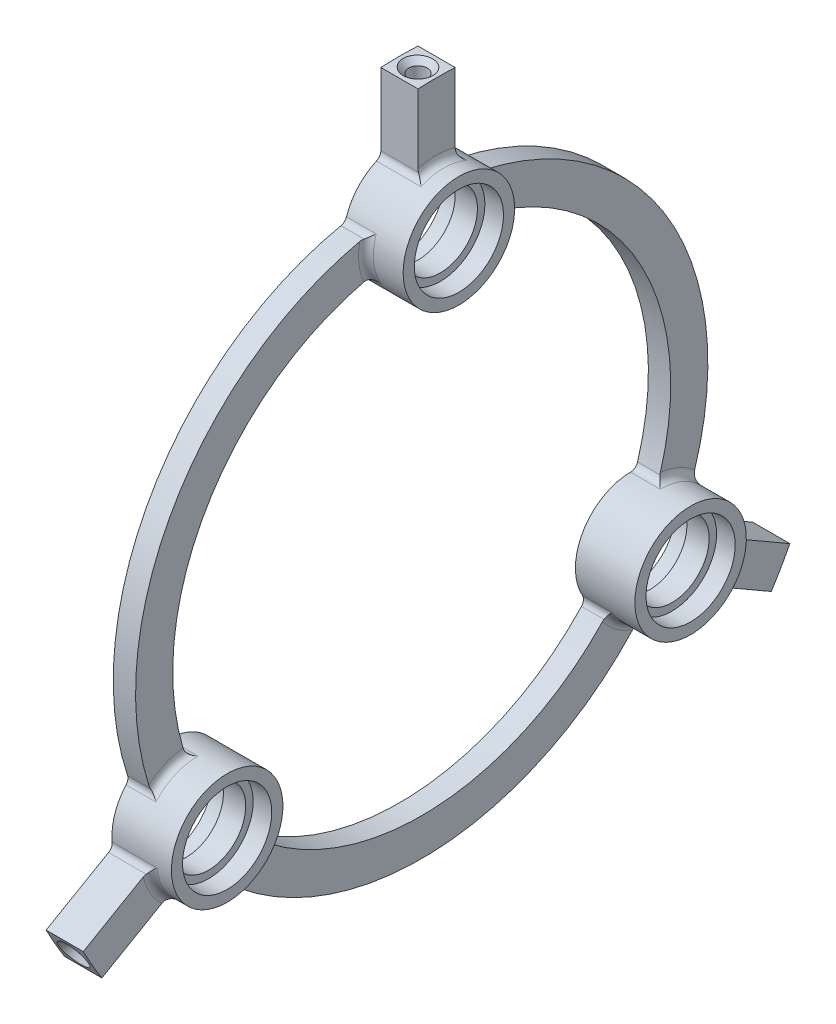
SolidWorks part; units mm, degrees
ref_plane "Спереди" through (0, 0, 0) normal (0, 0, 1) x (1, 0, 0)
ref_plane "Сверху" through (0, 0, 0) normal (0, 1, 0) x (1, 0, 0)
ref_plane "Справа" through (0, 0, 0) normal (1, 0, 0) x (0, 0, -1)
sketch "Эскиз3" plane through (0, 0, 0) normal (1, 0, 0) x (0, 0, -1)
  circle A0 centre (0, 0) radius 36 construction
  dimension "D1" = 72
sketch "Эскиз1" plane through (0, 0, 0) normal (1, 0, 0) x (0, 0, -1)
  line L0 (38.5, 0) -> (33.5, 0) construction
  circle A3 centre (0, 0) radius 38.5
  circle A4 centre (0, 0) radius 33.5
  circle A5 centre (0, 0) radius 36 construction
  point P9 (36, 0)
  dimension "D1" = 5
extrude "Бобышка-Вытянуть1" add sketch "Эскиз1" along normal blind 3
sketch "Эскиз2" plane through (0, 0, 0) normal (-1, 0, 0) x (0, 0, 1)
  circle A0 centre (0, 36) radius 7.5
  circle A1 centre (0, 0) radius 36 construction
  dimension "D1" = 15
extrude "Бобышка-Вытянуть2" add sketch "Эскиз2" against normal blind 8
sketch "Эскиз4" plane through (0, 0, 0) normal (-1, 0, 0) x (0, 0, 1)
  circle A0 centre (0, 36) radius 5
  dimension "D1" = 10
extrude "Вырез-Вытянуть1" cut sketch "Эскиз4" against normal through all
sketch "Эскиз5" plane through (0, 0, 0) normal (-1, 0, 0) x (0, 0, 1)
  circle A0 centre (0, 36) radius 6
  dimension "D1" = 12
extrude "Вырез-Вытянуть2" cut sketch "Эскиз5" against normal blind 2.5
sketch "Эскиз6" plane through (8, 0, 0) normal (1, 0, 0) x (0, 0, -1)
  circle A0 centre (0, 36) radius 6
  dimension "D1" = 12
extrude "Вырез-Вытянуть3" cut sketch "Эскиз6" against normal blind 2.5
sketch "Эскиз7" plane through (0, 0, 0) normal (-1, 0, 0) x (0, 0, 1)
  line L0 (0, 0) -> (0, 53.5) construction
  line L1 (-2.5, 53.4416) -> (-2.5, 43.0711)
  line L2 (2.5, 53.4416) -> (2.5, 43.0711)
  circle A0 centre (0, 0) radius 53.5 construction
  arc A1 (7.2794, 37.8056) -> (-7.2794, 37.8056) centre (0, 36) ccw construction
  arc A2 (-2.5, 53.4416) -> (2.5, 53.4416) centre (0, 0) cw
  arc A3 (-2.5, 43.0711) -> (2.5, 43.0711) centre (0, 36) cw
  point P13 (0, 0)
  dimension "D1" = 107
  dimension "D2" = 5
extrude "Бобышка-Вытянуть3" add sketch "Эскиз7" against normal blind 5
fillet "Скругление1" radius 1 9 edges at (3, 35.263, 7.4637) (3, 35.263, -7.4637) (1.5, 32.8056, -6.7857) (1.5, 32.8056, 6.7857) (1.5, 37.8056, 7.2794) (1.5, 37.8056, -7.2794) (5, 43.5, 0) (2.5, 43.0711, 2.5) (2.5, 43.0711, -2.5)
hole_wizard "Отверстие обработанное метчиком M31" positions "Трехмерный эскиз1" profile "Эскиз8" tap size "M3" standard "ISO"
sketch3d "Трехмерный эскиз1"
  line L2 (2.5, 53.4416, 2.5) -> (2.5, 53.4416, 0) construction
  line L3 (5, 53.4416, 2.5) -> (0, 53.4416, 2.5) construction
  line L7 (2.5, 53.4416, 0) -> (2.5, 53.5, 0) construction
  line L12 (0, 53.4416, 2.5) -> (0, 53.4416, -2.5) construction
  line L13 (2.5, 53.4416, 0) -> (0, 53.4416, 0) construction
  point P0 (2.5, 53.5, 0)
  point P50 (0, 53.4416, 0)
sketch "Эскиз8" plane through (2.5, 53.5, 0) normal (1, 0, 0) x (0, 0, 1)
  line L0 (0, 0) -> (0, 7.7511)
  line L1 (0, 7.7511) -> (1.25, 7)
  line L2 (1.25, 7) -> (1.25, 0.75)
  line L3 (1.25, 0.75) -> (2, 0)
  line L5 (2, 0) -> (0, 0)
  line L6 (-1.25, 0.75) -> (-2, 0) construction
  line L10 (0, 7.7511) -> (-1.25, 7) construction
  line L11 (0, -6.35) -> (0, 107.95) construction
  dimension "Диаметр сверла" = 2.5
  dimension "Глубина сверла" = 7
  dimension "Диаметр передней зенковки" = 4
  dimension "Угол передней зенковки" = 90
  dimension "Угол заточки сверла" = 118
cosmetic thread "Отверстие резьбы1" parameters "D1"=6, "D2"=3
pattern_circular "Круговой массив1" count 3 over 360 about axis through (3, 0, 0) along (-1, 0, 0) of "Бобышка-Вытянуть2", "Вырез-Вытянуть1", "Вырез-Вытянуть2", "Вырез-Вытянуть3", "Бобышка-Вытянуть3", "Скругление1", "Отверстие обработанное метчиком M31"
